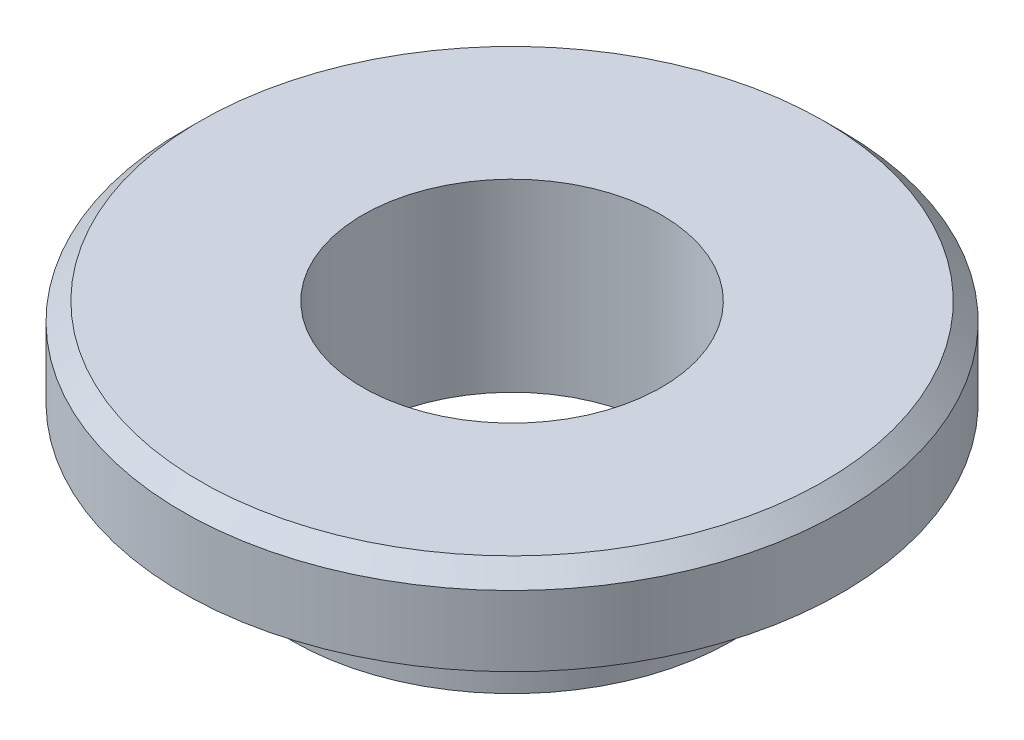
SolidWorks part; units mm, degrees
material "ABS"
ref_plane "Front Plane" through (0, 0, 0) normal (0, 0, 1) x (1, 0, 0)
ref_plane "Top Plane" through (0, 0, 0) normal (0, 1, 0) x (1, 0, 0)
ref_plane "Right Plane" through (0, 0, 0) normal (1, 0, 0) x (0, 0, -1)
ref_axis "Central Axis" through (0, -0.1333, 0) along (0, 1, 0)
sketch "Washer Revolve Profile" plane through (0, 0, 0) normal (0, 0, 1) x (1, 0, 0)
  line L0 (2.159, 2.667) -> (2.159, 0)
  line L1 (2.159, 0) -> (3.175, 0)
  line L2 (3.175, 0) -> (3.175, 1.397)
  line L3 (3.175, 1.397) -> (4.7625, 1.397)
  line L4 (4.7625, 1.397) -> (4.7625, 2.413)
  line L5 (4.5085, 2.667) -> (2.159, 2.667)
  line L6 (4.5085, 2.667) -> (4.7625, 2.413)
  line L7 (0, 0) -> (0, 2.667) construction
  line L9 (0, -0.1333) -> (0, 2.8003) construction
  dimension "D1" = 9.525
  dimension "D2" = 6.35
  dimension "D3" = 1.27
  dimension "D4" = 2.667
  dimension "D5" = 4.318
  dimension "D6" = 45
  dimension "D7" = 0.254
revolve "Washer Revolve" add sketch "Washer Revolve Profile" angle 360 about L7
